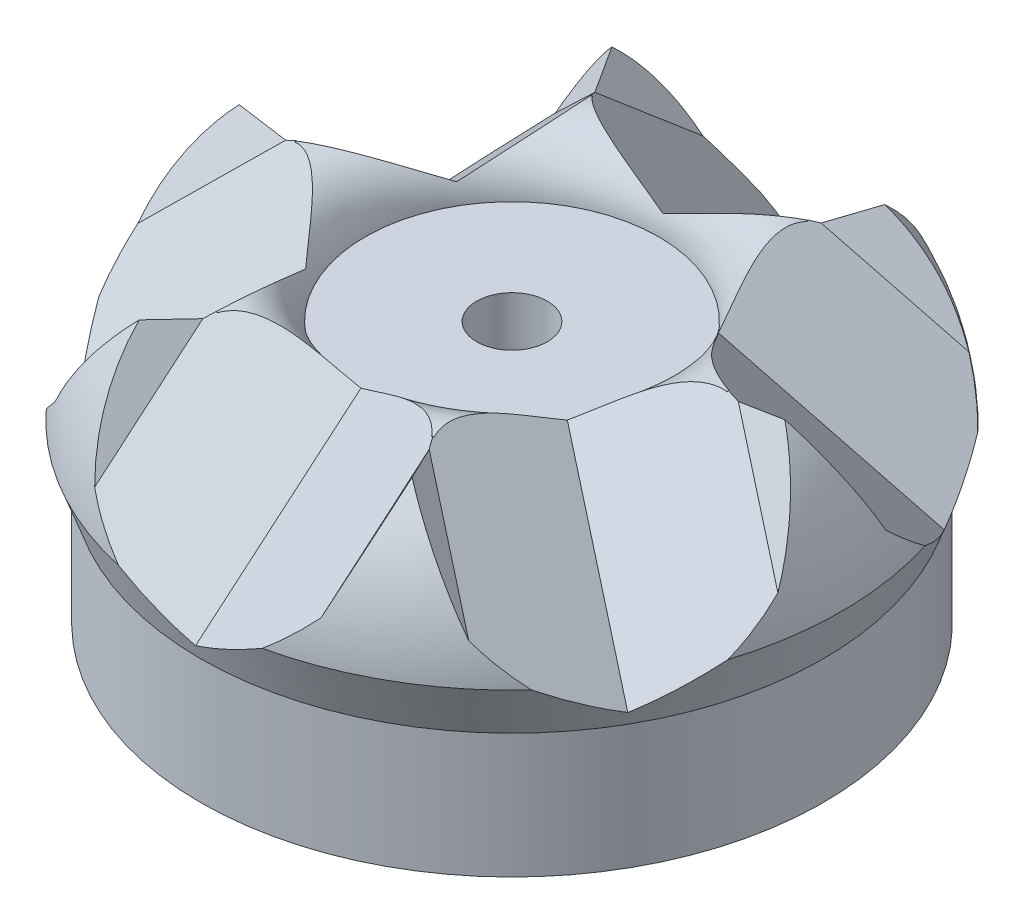
SolidWorks part; units mm, degrees
ref_plane "Front Plane" through (0, 0, 0) normal (0, 0, 1) x (1, 0, 0)
ref_plane "Top Plane" through (0, 0, 0) normal (0, 1, 0) x (1, 0, 0)
ref_plane "Right Plane" through (0, 0, 0) normal (1, 0, 0) x (0, 0, -1)
sketch "Sketch1" plane through (0, 0, 0) normal (0, 0, 1) x (1, 0, 0)
  line L0 (0, 0) -> (-15, 0)
  line L1 (-15, 0) -> (-15.8793, 2.4158)
  line L9 (0, 11.0042) -> (0, 0)
  arc A4 (-15.8793, 2.4158) -> (0, 11.0042) centre (-5.3734, 1.9651) cw
  point P6 (0, 0)
  dimension "D1" = 15
  dimension "D6" = 110
revolve "Revolve1" add sketch "Sketch1" angle 360 about L9
ref_plane "Plane1" through (0, -4.8209, 13.2453) normal (0, -0.342, 0.9397) x (1, 0, 0)
sketch "Sketch4" plane through (0, -4.8209, 13.2453) normal (0, -0.342, 0.9397) x (1, 0, 0)
  line L0 (0, 5.8427) -> (-5.4512, 8.3555)
  line L1 (-5.4512, 8.3555) -> (-7.7254, 11.6664)
  line L2 (-9.0446, 12.3358) -> (-6.5736, 15.7244)
  line L3 (-6.5736, 15.7244) -> (0, 17.6748)
  line L4 (0, 0) -> (0, 17.6748) construction
  line L5 (-7.7254, 11.6664) -> (-9.0446, 12.3358)
  line L6 (7.7254, 11.6664) -> (9.0446, 12.3358)
  line L7 (6.5736, 15.7244) -> (0, 17.6748)
  line L8 (9.0446, 12.3358) -> (6.5736, 15.7244)
  line L9 (5.4512, 8.3555) -> (7.7254, 11.6664)
  line L10 (0, 5.8427) -> (5.4512, 8.3555)
  line L11 (0, -1.6512) -> (0, 24.2997) construction
  line L12 (0, 2.2701) -> (0, 0) construction
  spline S1 degree 3 poles (0, 14.2) (-0.0091, 14.2) (-0.0678, 14.2) (-0.2092, 14.1994) (-0.5236, 14.1958) (-1.0382, 14.1821) (-1.7042, 14.1478) (-2.4239, 14.09) (-3.1163, 14.0146) (-3.7995, 13.9199) (-4.4752, 13.8059) (-5.1601, 13.6678) (-5.8519, 13.5034) (-6.5447, 13.3114) (-7.2116, 13.0977) (-7.8279, 12.8723) (-8.3893, 12.642) (-8.912, 12.4041) (-9.4272, 12.1452) (-9.9343, 11.8639) (-10.4465, 11.5502) (-10.9488, 11.2102) (-11.4527, 10.8325) (-11.9439, 10.4242) (-12.4204, 9.9834) (-12.8804, 9.5096) (-13.321, 9.0017) (-13.739, 8.4588) (-14.1314, 7.8817) (-14.4946, 7.2701) (-14.8243, 6.6247) (-15.1115, 5.961) (-15.3603, 5.2674) (-15.5665, 4.5453) (-15.7258, 3.7972) (-15.8209, 3.1295) (-15.8591, 2.682) (-15.8714, 2.4729) (-15.8746, 2.4131) (-15.8763, 2.3788) (-15.8771, 2.3594) (-15.8774, 2.3549) knots 0 0 0 0 0.001208 0.007777 0.018729 0.042873 0.076025 0.107367 0.139279 0.169584 0.200682 0.232672 0.265541 0.29906 0.332745 0.363467 0.391 0.417803 0.443874 0.471561 0.498582 0.527246 0.555408 0.5853 0.614841 0.644106 0.675218 0.706128 0.736871 0.769513 0.802024 0.834427 0.86674 0.900993 0.935178 0.969313 0.99138 0.995391 0.997396 0.999401 1 1 1 1 construction
  point P0 (-7.7254, 11.6664)
  point P6 (2.433, 11.5571)
  point P7 (0, 9.7323)
  point P16 (3.7431, 15.1131)
  point P17 (-6.4101, 21.4765)
  point P18 (-7.5331, 23.0673)
  point P19 (-5.1, 21.6168)
  point P20 (-6.6909, 23.2077)
  point P21 (-3.0881, 16.7039)
  point P22 (-1.6844, 14.2709)
  point P23 (0, 12.3993)
  point P28 (-8.556, 30.5648)
  point P29 (-5.2612, 26.207)
  point P30 (-3.2417, 20.4676)
sketch "Sketch5" plane through (0, 0, 0) normal (0, 1, 0) x (1, 0, 0)
  line L1 (3.5355, 3.5355) -> (-3.5355, 3.5355) construction
  line L2 (3.5355, 3.5355) -> (3.5355, -3.5355) construction
  line L3 (3.5355, -3.5355) -> (-3.5355, -3.5355) construction
  line L4 (-3.5355, 3.5355) -> (-3.5355, -3.5355) construction
  line L5 (3.5355, 3.5355) -> (-3.5355, -3.5355) construction
  line L6 (3.5355, -3.5355) -> (-3.5355, 3.5355) construction
  circle A0 centre (0, 0) radius 5
  dimension "D1" = 10
sketch "Sketch6" plane through (0, 0, 0) normal (0, 1, 0) x (1, 0, 0)
  line L0 (0, 7.435) -> (0, -7.1989) construction
sketch "Sketch11" plane through (0, 0, 0) normal (0, 1, 0) x (1, 0, 0)
  line L0 (3.5355, -3.5355) -> (-3.5355, 3.5355) construction
  circle A0 centre (0, 0) radius 1.7
  dimension "D1" = 3.4
extrude "Cut-Extrude2" cut sketch "Sketch11" along normal blind 10 and the other way through all
sketch "Sketch13" plane through (0, 10, 0) normal (0, -1, 0) x (1, 0, 0)
  circle A0 centre (0, 0) radius 5
  dimension "D1" = 10
extrude "Cut-Extrude3" cut sketch "Sketch13" against normal through all
sketch "Sketch14" plane through (0, 0, 0) normal (1, 0, 0) x (0, 0, -1)
  line L0 (-26.1018, 0) -> (0, 22.1584)
  point P2 (0, 22.331)
  point P3 (-0.3441, 27.5081)
  point P4 (0, 22.1584)
sweep "Cut-Sweep2" cut profiles "Sketch4" path "Sketch14"
pattern_circular "CirPattern1" count 6 over 360 about axis through (0, 2.4158, 0) along (0, -1, 0) of "Cut-Sweep2" reverse direction yes
sketch "Sketch15" plane through (0, 0, 0) normal (1, 0, 0) x (0, 0, -1)
  line L0 (-7.0667, 6.5733) -> (0, 6.5733)
  line L1 (0, 6.5733) -> (0, 13.8258)
  line L2 (0, 13.8258) -> (-10.4142, 13.8258)
  line L3 (-10.4142, 13.8258) -> (-10.4142, 8.8655)
  line L4 (-11.3866, 9.0454) -> (-9.4418, 8.6856) construction
  arc A0 (-10.4142, 8.8655) -> (-7.0667, 6.5733) centre (-9.654, 6.3853) cw
  point P4 (-13.2056, 26.4213)
  point P5 (-4.315, 9.4247)
  point P9 (-8.6553, 16.7336)
  point P10 (-12.9691, 20.4315)
  point P11 (-7.7086, 23.9918)
  point P12 (-4.4443, 18.2838)
  point P13 (-11.1188, 26.5466)
  point P14 (-7.8633, 12.3716)
  point P15 (-5.6733, 8.4902)
  point P16 (-12.4486, 26.1755)
  point P17 (-6.8175, 18.4564)
  point P18 (-12.4765, 26.1657)
  point P19 (-9.3273, 11.7454)
  point P20 (-5.8838, 6.6592)
  point P21 (-9.8951, 10.1578)
revolve "Cut-Revolve1" cut sketch "Sketch15" angle 360 about L1
sketch "Sketch16" plane through (0, 0, 0) normal (0, 1, 0) x (1, 0, 0)
  line L0 (3.5355, 3.5355) -> (-3.5355, -3.5355) construction
  circle A0 centre (0, 0) radius 15
  circle A1 centre (0, 0) radius 1.7
  circle A2 centre (0, 0) radius 15 construction
extrude "Boss-Extrude1" add sketch "Sketch16" against normal blind 6
sketch "Sketch17" plane through (0, 0, 0) normal (0, 1, 0) x (1, 0, 0)
  circle A0 centre (0, 0) radius 15.8793 construction
